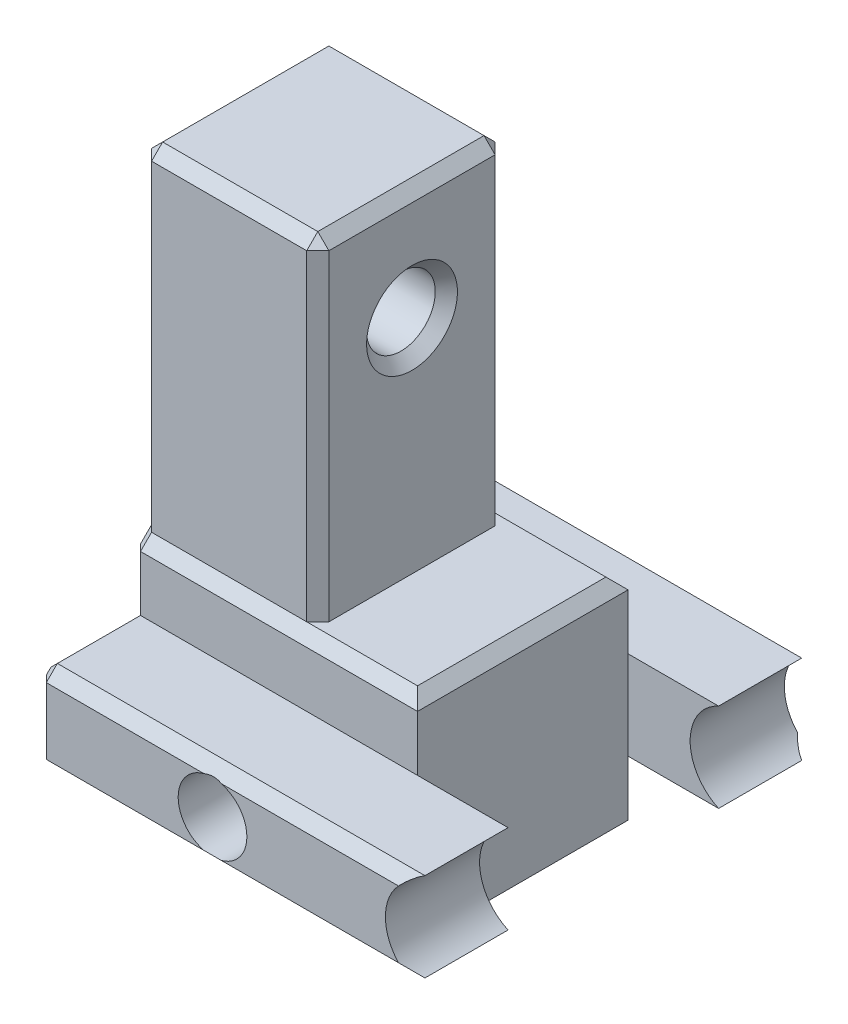
SolidWorks part; units mm, degrees
ref_plane "Front Plane" through (0, 0, 0) normal (0, 0, 1) x (1, 0, 0)
ref_plane "Top Plane" through (0, 0, 0) normal (0, 1, 0) x (1, 0, 0)
ref_plane "Right Plane" through (0, 0, 0) normal (1, 0, 0) x (0, 0, -1)
sketch "Sketch1" plane through (0, 0, 0) normal (0, 0, 1) x (1, 0, 0)
  line L0 (-0.9165, 2) -> (-50, 2)
  line L1 (-50, 2) -> (-50, -2)
  line L3 (-50, -2) -> (-0.9165, -2)
  arc A0 (-0.9165, 2) -> (-0.9165, -2) centre (0, 0) ccw
  dimension "D2" = 4
  dimension "D1" = 2.2
  dimension "D3" = 2
  dimension "D4" = 50
extrude "Boss-Extrude1" add sketch "Sketch1" along normal blind 18
sketch "Sketch2" plane through (-50, 0, 0) normal (-1, 0, 0) x (0, 0, 1)
  line L1 (4.25, 5) -> (13.75, 5)
  line L2 (4.25, 5) -> (4.25, -5)
  line L3 (4.25, -5) -> (13.75, -5)
  line L4 (13.75, 5) -> (13.75, -5)
  line L6 (18, 2) -> (18, -2) construction
  line L7 (18, 2) -> (0, 2) construction
  point P4 (4.25, 0)
  point P7 (18, 0)
  point P8 (9, 5)
  point P11 (9, 2)
  dimension "D1" = 9.5
  dimension "D3" = 10
extrude "Boss-Extrude2" add sketch "Sketch2" against normal up to vertex (49.0835 mm away) up to point (-0.9165, 2, 0)
sketch "Sketch3" plane through (0, 2, 0) normal (0, 1, 0) x (1, 0, 0)
  line L1 (-0.9165, -4.25) -> (4.0835, -4.25)
  line L2 (-0.9165, -4.25) -> (-0.9165, -13.75)
  line L3 (-0.9165, -13.75) -> (4.0835, -13.75)
  line L4 (4.0835, -4.25) -> (4.0835, -13.75)
  dimension "D1" = 9.5
  dimension "D2" = 5
sketch "Sketch4" plane through (0, 0, 18) normal (0, 0, 1) x (1, 0, 0)
  line L0 (-0.9165, 2) -> (-50, 2) construction
  point P0 (-10, 0)
  dimension "D1" = 10
  dimension "D2" = 2
hole_wizard "M3 Clearance Hole1" positions "Sketch5" profile "Sketch6" hole size "M3" standard "DIN" end condition through all
sketch "Sketch5" plane through (0, 0, 18) normal (0, 0, 1) x (1, 0, 0)
  point P0 (-10, 0)
sketch "Sketch6" plane through (-10, 0, 18) normal (1, 0, 0) x (0, -1, 0)
  line L0 (0, 0) -> (0, 18)
  line L1 (0, 18) -> (1.55, 18)
  line L2 (1.55, 18) -> (1.55, 0)
  line L5 (1.55, 0) -> (0, 0)
  line L11 (0, -6.35) -> (0, 107.95) construction
  dimension "Thru Hole Dia." = 3.1
  dimension "Thru Hole Depth" = 18
sketch "Sketch7" plane through (-50, 0, 0) normal (-1, 0, 0) x (0, 0, 1)
  line L0 (0, 2) -> (0, -2)
  line L1 (0, -2) -> (4.25, -2)
  line L2 (4.25, -2) -> (4.25, -5)
  line L3 (4.25, -5) -> (13.75, -5)
  line L4 (13.75, -5) -> (13.75, -2)
  line L5 (13.75, -2) -> (18, -2)
  line L6 (18, -2) -> (18, 2)
  line L7 (18, 2) -> (13.75, 2)
  line L8 (13.75, 2) -> (13.75, 5)
  line L9 (13.75, 5) -> (4.25, 5)
  line L10 (4.25, 5) -> (4.25, 2)
  line L11 (4.25, 2) -> (0, 2)
extrude "Boss-Extrude3" add sketch "Sketch7" along normal blind 1.5
chamfer "Chamfer1" distance 0.5 angle 45 8 edges at (-26.2083, -5, 4.25) (-26.2083, -5, 13.75) (-26.2083, 5, 13.75) (-26.2083, 5, 4.25) (-26.2083, -2, 0) (-26.2083, 2, 0) (-26.2083, -2, 18) (-26.2083, 2, 18)
sketch "Sketch8" plane through (0, 5, 0) normal (0, 1, 0) x (1, 0, 0)
  line L0 (-51.5, -4.25) -> (-0.9165, -4.25) construction
  line L1 (0, -4.25) -> (-5, -4.25)
  line L2 (0, -4.25) -> (0, -13.75)
  line L3 (0, -13.75) -> (-5, -13.75)
  line L4 (-5, -4.25) -> (-5, -13.75)
  line L5 (-0.9165, -13.75) -> (-51.5, -13.75) construction
  dimension "D1" = 5
extrude "Cut-Extrude1" cut sketch "Sketch8" against normal through all
sketch "Sketch9" plane through (0, 5, 0) normal (0, 1, 0) x (1, 0, 0)
  line L0 (-5, -4.75) -> (-51.5, -4.75) construction
  line L1 (-10, -4.75) -> (-18, -4.75)
  line L2 (-10, -4.75) -> (-10, -13.25)
  line L3 (-10, -13.25) -> (-18, -13.25)
  line L4 (-18, -4.75) -> (-18, -13.25)
  line L5 (-51.5, -13.25) -> (-5, -13.25) construction
  line L6 (-5, -4.75) -> (-5, -13.25) construction
  line L8 (0, 0) -> (0, -18.6346) construction
  dimension "D1" = 5
  dimension "D2" = 18
extrude "Boss-Extrude4" add sketch "Sketch9" along normal blind 15
sketch "Sketch10" plane through (-10, 0, 0) normal (-1, 0, 0) x (0, 0, 1)
  line L1 (4.75, 5) -> (13.25, 5) construction
  line L2 (4.75, 20) -> (13.25, 20) construction
  circle A0 centre (9, 15) radius 1.55
  point P7 (9, 20)
  dimension "D1" = 3.1
  dimension "D2" = 10
sketch "Sketch13" plane through (0, 20, 0) normal (0, 1, 0) x (1, 0, 0)
  line L0 (-18, -4.75) -> (-18, -13.25) construction
  line L1 (-51.5, 0) -> (-18, 0)
  line L2 (-51.5, 0) -> (-51.5, -18)
  line L3 (-51.5, -18) -> (-18, -18)
  line L4 (-18, 0) -> (-18, -18)
  line L5 (-10.3905, -18) -> (-51.5, -18) construction
  line L6 (-51.5, 0) -> (-10.3905, 0) construction
  line L7 (-51.5, -13.25) -> (-51.5, -4.75) construction
extrude "Cut-Extrude5" cut sketch "Sketch13" against normal through all
extrude "Cut-Extrude6" cut sketch "Sketch10" along normal blind 2.6
chamfer "Chamfer2" distance 0.5 angle 45 30 edges at (-5, -5, 9) (-5, 5, 9) (-14, 20, 13.25) (-18, 20, 9) (-18, 12.5, 13.25) (-18, 4.75, 13.5) (-18, 3.25, 13.75) (-18, 2, 15.625) (-18, 1.75, 17.75) (-18, 0, 18) (-18, -1.75, 17.75) (-18, -2, 15.625) (-18, -3.25, 13.75) (-18, -4.75, 13.5) (-18, -5, 9) (-18, -4.75, 4.5) (-18, -3.25, 4.25) (-18, -2, 2.375) (-18, -1.75, 0.25) (-18, 0, 0) (-18, 1.75, 0.25) (-18, 2, 2.375) (-18, 3.25, 4.25) (-18, 4.75, 4.5) (-18, 12.5, 4.75) (-14, 20, 4.75) (-10, 12.5, 13.25) (-10, 20, 9) (-10, 12.5, 4.75) (-10, 15, 10.55)
